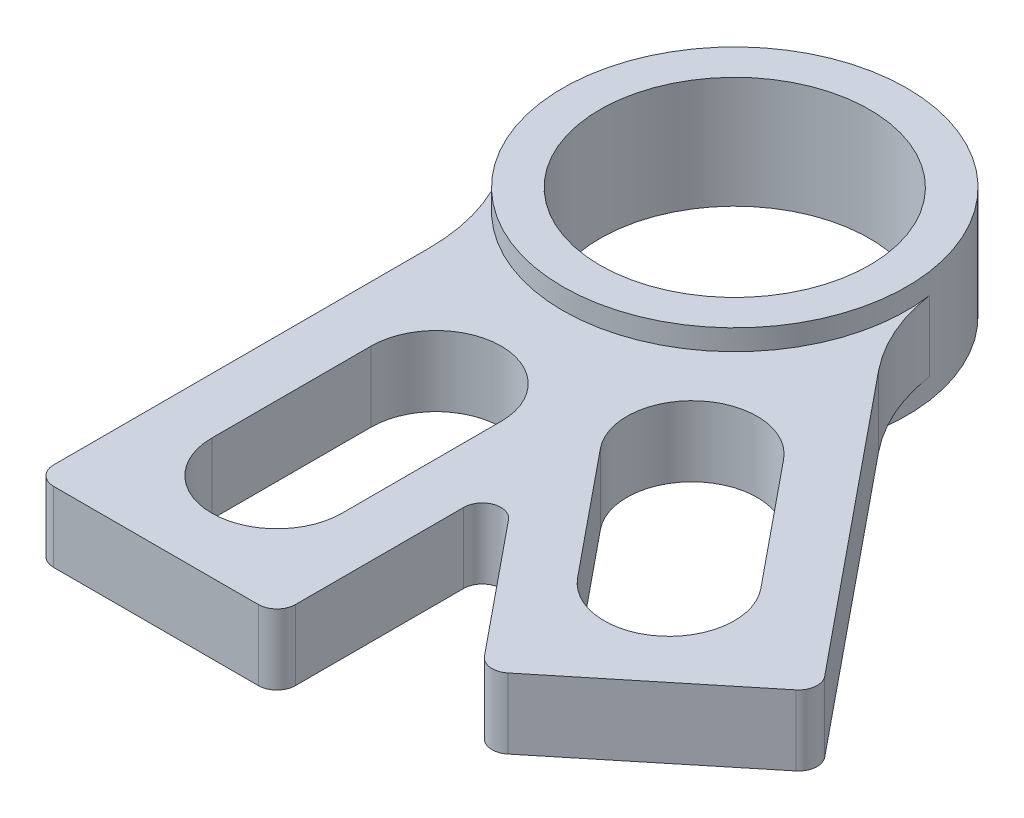
SolidWorks part; units mm, degrees
material "AISI 4130 Steel, annealed at 865C"
ref_plane "Front Plane" through (0, 0, 0) normal (0, 0, 1) x (1, 0, 0)
ref_plane "Top Plane" through (0, 0, 0) normal (0, 1, 0) x (1, 0, 0)
ref_plane "Right Plane" through (0, 0, 0) normal (1, 0, 0) x (0, 0, -1)
sketch "Sketch1" plane through (0, 0, 0) normal (0, 1, 0) x (1, 0, 0)
  line L0 (0, 0) -> (0, -49.3903) construction
  line L1 (0, 0) -> (31.209, -38.2806) construction
  line L2 (-10.3188, -49.3903) -> (10.3188, -49.3903)
  line L3 (10.3188, -49.3903) -> (10.3187, -28.987)
  line L4 (-10.3188, -49.3903) -> (-10.3187, -10.4432)
  line L5 (10.3187, -28.987) -> (23.2113, -44.8008)
  line L6 (23.2113, -44.8008) -> (39.2066, -31.7603)
  line L7 (39.2066, -31.7603) -> (14.5966, -1.5739)
  line L8 (-5.5563, -25.4826) -> (-5.5563, -39.0715)
  line L9 (5.5563, -25.4825) -> (5.5562, -39.0715)
  line L10 (11.7956, -23.2615) -> (20.3823, -33.7938)
  line L11 (20.4085, -16.2397) -> (28.9952, -26.772)
  line L12 (11.7956, -23.2615) -> (20.4085, -16.2397)
  circle A0 centre (0, 0) radius 11.5062
  circle A1 centre (0, 0) radius 14.6812
  arc A2 (-5.5563, -25.4826) -> (5.5563, -25.4825) centre (0, -25.4826) cw
  arc A3 (-5.5563, -39.0715) -> (5.5562, -39.0715) centre (0, -39.0715) ccw
  arc A4 (11.7956, -23.2615) -> (20.4085, -16.2397) centre (16.102, -19.7506) cw
  arc A5 (20.3823, -33.7938) -> (28.9952, -26.772) centre (24.6887, -30.2829) ccw
  point P9 (0, -49.3903)
  point P11 (31.209, -38.2806)
  point P20 (0, -44.6278)
  point P22 (0, -22.2633)
  point P29 (35.1858, -21.9615)
  point P30 (27.9118, -21.6338)
  point P31 (28.1996, -34.5893)
  point P32 (29.0098, -23.7118)
  point P33 (46.5597, -19.5989)
  point P34 (0, -19.9263)
  dimension "D1" = 23.0124
  dimension "D2" = 29.3624
  dimension "D9" = 4.7625
  dimension "D8" = 29.464
  dimension "D3" = 20.6375
  dimension "D4" = 49.3903
  dimension "D5" = 4.7625
  dimension "D6" = 13.589
  dimension "D7" = 4.7625
  dimension "D10" = 39.189
extrude "Boss-Extrude1" add sketch "Sketch1" along normal blind 4.7625 and the other way blind 4.7625 contours A1 A0 region at (-5.4988, 0, -13.1636)
extrude "Boss-Extrude2" add sketch "Sketch1<4>" along normal blind 2.9972 and the other way blind 2.9972 contours A1 L4 L2 L3 L5 L6 L7 A5 L10 A4 L11 A3 L8 A2 L9 region at (10.1012, 0, 28.3759)
sketch "Sketch1<4>" plane through (0, 0, 0) normal (0, 1, 0) x (1, 0, 0) same geometry as "Sketch1"
fillet "Fillet1" radius 16.002 2 edges at (-10.3187, 0, 10.4432) (14.5966, 0, 1.5739)
fillet "Fillet2" radius 1.5875 5 edges at (39.2066, 0, 31.7603) (23.2113, 0, 44.8008) (10.3187, 0, 28.987) (10.3188, 0, 49.3903) (-10.3188, 0, 49.3903)
